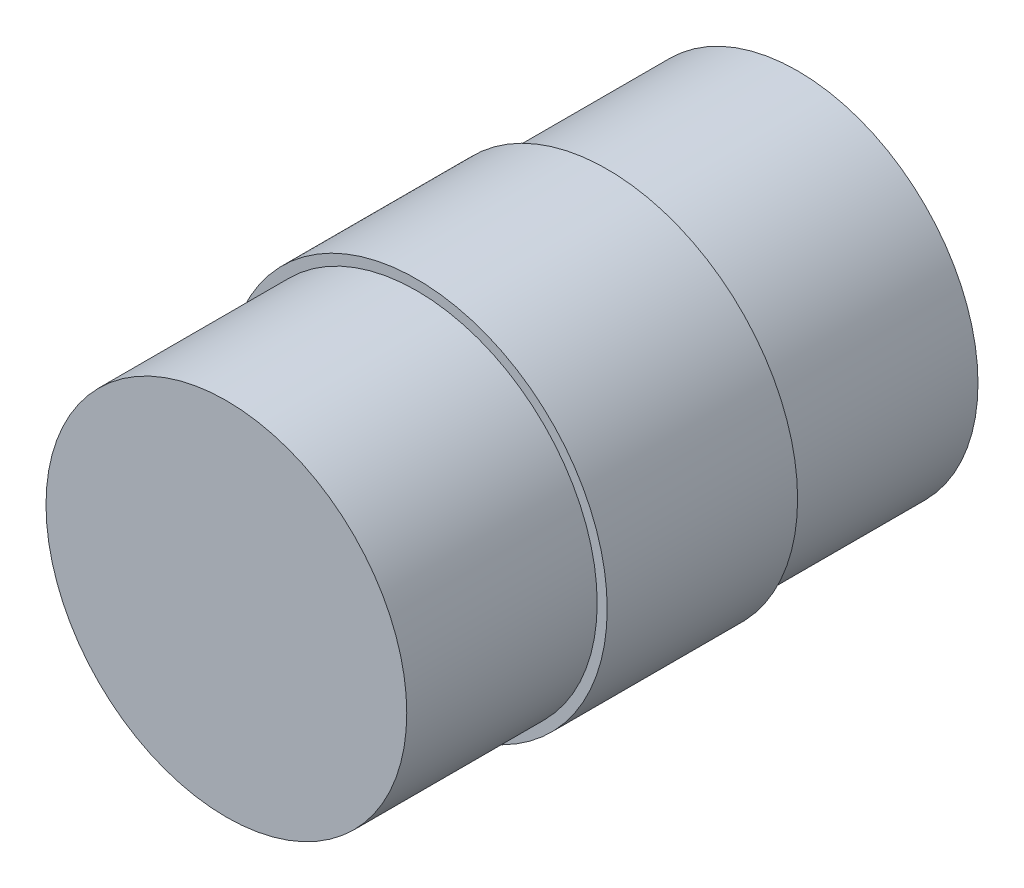
SolidWorks part; units mm, degrees
ref_plane "Front Plane" through (0, 0, 0) normal (0, 0, 1) x (1, 0, 0)
ref_plane "Top Plane" through (0, 0, 0) normal (0, 1, 0) x (1, 0, 0)
ref_plane "Right Plane" through (0, 0, 0) normal (1, 0, 0) x (0, 0, -1)
sketch "Sketch1" plane through (0, 0, 0) normal (0, 0, 1) x (1, 0, 0)
  circle A0 centre (0, 0) radius 19
  circle A1 centre (0, 0) radius 18
  dimension "D1" = 38
  dimension "D2" = 36
extrude "Boss-Extrude1" add sketch "Sketch1" along normal blind 19 contours A1 | A0
extrude "Boss-Extrude2" add sketch "Sketch1<3>" along normal blind 38 and the other way blind 19 contours A1 region at (0, 0, 0)
sketch "Sketch1<3>" plane through (0, 0, 0) normal (0, 0, 1) x (1, 0, 0) same geometry as "Sketch1"
sketch "Sketch2" plane through (0, 0, -19) normal (0, 0, -1) x (-1, 0, 0)
  circle A0 centre (0, 0) radius 2.5
  dimension "D1" = 5
extrude "Boss-Extrude3" add sketch "Sketch2" along normal blind 10
